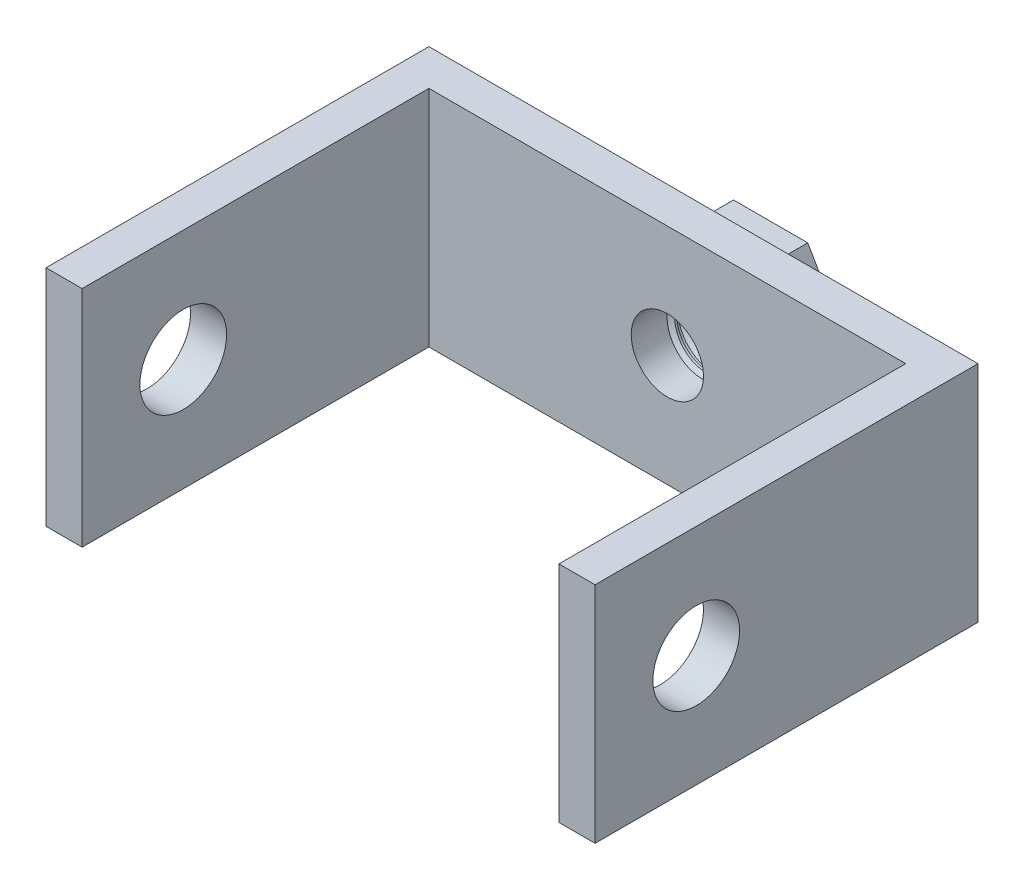
SolidWorks part; units mm, degrees
ref_plane "Front Plane" through (0, 0, 0) normal (0, 0, 1) x (1, 0, 0)
ref_plane "Top Plane" through (0, 0, 0) normal (0, 1, 0) x (1, 0, 0)
ref_plane "Right Plane" through (0, 0, 0) normal (1, 0, 0) x (0, 0, -1)
sketch "Sketch1" plane through (0, 0, 0) normal (0, 1, 0) x (1, 0, 0)
  line L0 (-33, 0) -> (33, 0)
  line L1 (33, 0) -> (33, -58)
  line L2 (33, -58) -> (38, -58)
  line L3 (38, -58) -> (38, 5)
  line L4 (38, 5) -> (-38, 5)
  line L5 (-38, 5) -> (-38, -58)
  line L6 (-38, -58) -> (-33, -58)
  line L7 (-33, -58) -> (-33, 0)
  dimension "D1" = 5
  dimension "D2" = 5
  dimension "D3" = 66
  dimension "D4" = 58
extrude "Boss-Extrude1" add sketch "Sketch1" along normal blind 31
hole_wizard "Ø12.0 mm Dowel Holes1" positions "Sketch2" profile "Sketch4" hole size "Ø12.0" standard "ISO" end condition through all
sketch "Sketch2" plane through (38, 0, 0) normal (1, 0, 0) x (0, 0, -1)
  line L0 (-58, 31) -> (-58, 0) construction
  line L1 (-58, 31) -> (5, 31) construction
  line L3 (-34, 31) -> (-34, 0) construction
  line L4 (-58, 0) -> (5, 0) construction
  point P0 (-34, 15.5)
  point P18 (0, 0)
  dimension "D1" = 24
sketch "Sketch4" plane through (38, 15.5, 34) normal (0, 1, 0) x (0, 0, -1)
  line L0 (0, 0) -> (0, 76)
  line L1 (0, 76) -> (6, 76)
  line L2 (6, 76) -> (6, 0)
  line L5 (6, 0) -> (0, 0)
  line L11 (0, -6.35) -> (0, 107.95) construction
  dimension "Thru Hole Dia." = 12
  dimension "Thru Hole Depth" = 76
hole_wizard "Ø10.0 mm Dowel Holes1" positions "Sketch5" profile "Sketch6" hole size "Ø10.0" standard "ISO" end condition through all
sketch "Sketch5" plane through (0, 0, -5) normal (0, 0, -1) x (-1, 0, 0)
  line L0 (38, 0) -> (-38, 31) construction
  line L2 (-38, 0) -> (38, 31) construction
  point P0 (0, 15.5)
  point P15 (0, 0)
sketch "Sketch6" plane through (0, 15.5, -5) normal (1, 0, 0) x (0, 1, 0)
  line L0 (0, 0) -> (0, 63)
  line L1 (0, 63) -> (5, 63)
  line L2 (5, 63) -> (5, 0)
  line L5 (5, 0) -> (0, 0)
  line L11 (0, -6.35) -> (0, 107.95) construction
  dimension "Thru Hole Dia." = 10
  dimension "Thru Hole Depth" = 63
sketch "Sketch7" plane through (0, 0, -5) normal (0, 0, -1) x (-1, 0, 0)
  line L0 (-38, 0) -> (38, 0) construction
  line L1 (10.2768, 15.5) -> (5.1384, 24.4)
  line L2 (5.1384, 24.4) -> (-5.1384, 24.4)
  line L3 (-5.1384, 24.4) -> (-10.2768, 15.5)
  line L4 (-10.2768, 15.5) -> (-5.1384, 6.6)
  line L5 (-5.1384, 6.6) -> (5.1384, 6.6)
  line L6 (5.1384, 6.6) -> (10.2768, 15.5)
  circle A0 centre (0, 15.5) radius 8.9 construction
  circle A1 centre (0, 15.5) radius 5
  dimension "D1" = 17.8
extrude "Boss-Extrude2" add sketch "Sketch7" along normal blind 9.3
thread "Thread1" pitch 1.25 method extrude profile "Thread Profile1" start angle 0, offset 0, length 9.3, pitch 1.5, diameter 10
ref_plane "Plane1" through (5, 15.5, -14.3) normal (0, -1, 0) x (1, 0, 0)
sketch "Thread Profile1" plane through (5, 15.5, -14.3) normal (0, -1, 0) x (1, 0, 0)
  line L0 (0, 0) -> (0, 1.25) construction
  line L11 (0, 0) -> (0, 1.0937)
  line L12 (0, 1.0937) -> (-0.6766, 0.7031)
  line L13 (-0.6766, 0.7031) -> (-0.6766, 0.3906)
  line L15 (-0.6766, 0.3906) -> (0, 0)
  line L17 (-0.6766, 0.5469) -> (0, 0.5469) construction
  point P2 (0, 0)
  dimension "Pitch" = 1.25
  dimension "Profile_Angle" = 60
  dimension "Profile_Land" = 0.3125
  dimension "Profile_Height" = 0.6766
sketch "Sketch13" plane through (0, 0, 58) normal (0, 0, 1) x (1, 0, 0)
  line L1 (-38, 31) -> (38, 31)
  line L2 (-38, 31) -> (-38, 0)
  line L3 (-38, 0) -> (38, 0)
  line L4 (38, 31) -> (38, 0)
extrude "Cut-Extrude1" cut sketch "Sketch13" against normal blind 10
